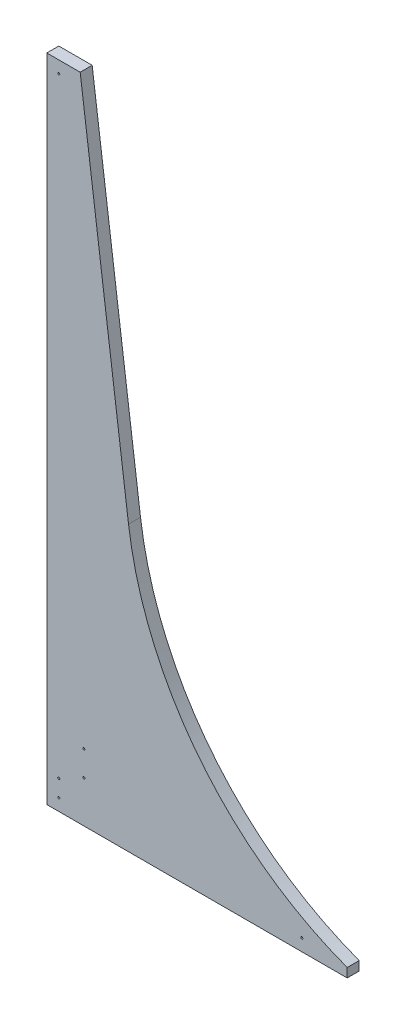
SolidWorks part; units mm, degrees
material "Pine"
ref_plane "Front Plane" through (0, 0, 0) normal (0, 0, 1) x (1, 0, 0)
ref_plane "Top Plane" through (0, 0, 0) normal (0, 1, 0) x (1, 0, 0)
ref_plane "Right Plane" through (0, 0, 0) normal (1, 0, 0) x (0, 0, -1)
sketch "Sketch1" plane through (0, 0, 0) normal (0, 0, 1) x (1, 0, 0)
  line L0 (0, 0) -> (500, 0)
  line L1 (0, 0) -> (0, 990.6)
  line L3 (0, 990.6) -> (50.8, 990.6)
  line L4 (50.8, 990.6) -> (124.3674, 431.8)
  line L7 (457.201, 13.862) -> (457.201, 0)
  circle A1 centre (18.2562, 18.2562) radius 1.5875
  circle A2 centre (388.1438, 18.2562) radius 1.5875
  circle A3 centre (18.2562, 972.3438) radius 1.5875
  circle A4 centre (56.3562, 101.6) radius 1.5875
  circle A6 centre (18.2562, 43.6562) radius 1.5875
  circle A7 centre (56.3562, 63.5) radius 1.5875
  arc A9 (124.3674, 431.8) -> (500, 0) centre (638.1166, 499.4364) ccw
  dimension "D7" = 3.175
  dimension "D8" = 18.2562
  dimension "D10" = 18.2562
  dimension "D11" = 3.175
  dimension "D12" = 18.2562
  dimension "D14" = 3.175
  dimension "D15" = 25.4
  dimension "D16" = 18.2562
  dimension "D17" = 101.6
  dimension "D18" = 50.8
  dimension "D24" = 3.175
  dimension "D1" = 500
  dimension "D2" = 990.6
  dimension "D3" = 42.799
  dimension "D4" = 50.8
  dimension "D5" = 558.8
  dimension "D6" = 97.5
  dimension "D9" = 18.2562
  dimension "D13" = 18.2562
  dimension "D20" = 38.1
  dimension "D21" = 38.1
extrude "Boss-Extrude1" add sketch "Sketch1" along normal blind 18.2562 contours A9 L4 L3 L1 L0 L7 A7 A6 A4 A3 A2 A1 region at (107.6408, 331.3665, 0)
